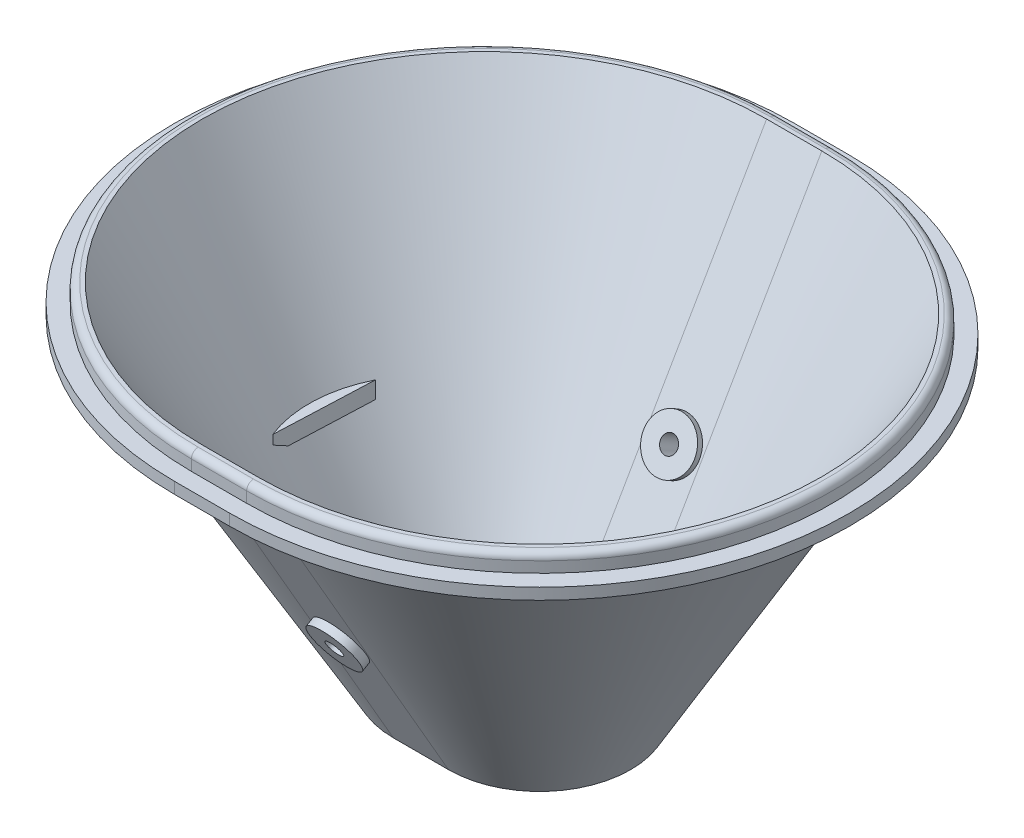
SolidWorks part; units mm, degrees
ref_plane "Front Plane" through (0, 0, 0) normal (0, 0, 1) x (1, 0, 0)
ref_plane "Top Plane" through (0, 0, 0) normal (0, 1, 0) x (1, 0, 0)
ref_plane "Right Plane" through (0, 0, 0) normal (1, 0, 0) x (0, 0, -1)
sketch3d "3DSketch3"
  line L0 (3.059, 15.8968, -14.5607) -> (7.0226, 15.8968, -14.5607)
  line L1 (7.0226, 15.8968, 14.5607) -> (-2.0226, 15.8968, 14.5607)
  line L2 (-1.9193, 15.8968, -14.5607) -> (3.059, 15.8968, -14.5607)
  arc A0 (7.0226, 15.8968, -14.5607) -> (7.0226, 15.8968, 14.5607) centre (5, 15.8968, 0) cw
  arc A3 (-2.0226, 15.8968, 14.5607) -> (-1.9193, 15.8968, -14.5607) centre (-0.0092, 15.8968, 0.007) cw
  point P3 (5, 1.1963, 0)
  point P7 (-0.0092, 1.2044, 0.007)
sketch3d "3DSketch2"
  line L0 (3.0806, 16.4804, -13.5499) -> (6.9193, 16.4804, -13.5499)
  line L1 (4.7004, 16.4804, 13.6773) -> (-0.7631, 16.4804, 13.6773)
  line L2 (-1.9193, 16.4804, -13.5499) -> (3.0806, 16.4804, -13.5499)
  arc A0 (6.9193, 16.4804, -13.5499) -> (4.7004, 16.4804, 13.6773) centre (5.0285, 16.4804, 0) cw
  arc A1 (-0.7631, 16.4804, 13.6773) -> (-1.9193, 16.4804, -13.5499) centre (0.1584, 16.4804, 0) cw
  point P5 (5.0285, 2.7991, 0)
  point P11 (0.1584, 2.772, 0)
sketch "Sketch3" plane through (0, 0, 0) normal (1, 0, 0) x (0, 0, -1)
  line L0 (13.5499, 16.4804) -> (4.7863, 0.7578)
  line L1 (4.7863, 0.7578) -> (5.7863, 0.7578)
  line L2 (5.7863, 0.7578) -> (14.6001, 16.5704)
  line L3 (18.971, 24.4121) -> (21.8382, 24.4121)
  line L4 (21.8382, 24.4121) -> (21.8382, 25.4121)
  line L5 (21.8382, 25.4121) -> (20.3382, 25.4121)
  line L6 (20.3382, 25.4121) -> (20.3382, 26.3621)
  line L7 (19.7382, 26.9621) -> (19.3923, 26.9621)
  line L8 (19.3923, 26.9621) -> (13.5499, 16.4804)
  line L9 (14.6001, 16.5704) -> (18.971, 24.4121)
  arc A0 (20.3382, 26.3621) -> (19.7382, 26.9621) centre (19.7382, 26.3621) ccw
  dimension "D7" = 0.6
  dimension "D1" = 0.3459
  dimension "D2" = 18
  dimension "D3" = 1
  dimension "D4" = 1
  dimension "D5" = 1.5
  dimension "D6" = 0.95
  dimension "D8" = 180
  dimension "D9" = 12
ref_plane "Plane for horizontal sketch" through (0, 16.4804, 0) normal (0, 1, 0) x (1, 0, 0)
sketch "Sketch4" plane through (0, 16.4804, 0) normal (0, 1, 0) x (1, 0, 0)
  line L3 (5.0285, -17.4227) -> (0.1584, -17.4227)
  line L4 (0.1584, 15.5773) -> (5.0285, 15.5773)
  arc A2 (0.1584, -17.4227) -> (0.1584, 15.5773) centre (0.1584, -0.9227) cw
  arc A3 (5.0285, 15.5773) -> (5.0285, -17.4227) centre (5.0285, -0.9227) cw
  dimension "D1" = 33
ref_plane "Plane for vertical sketch" through (0.1584, 0, 0) normal (1, 0, 0) x (0, 0, -1)
sketch "Sketch6" plane through (0.1584, 0, 0) normal (1, 0, 0) x (0, 0, -1)
  line L0 (15.5773, 16.4804) -> (6.1753, 0.1956)
  line L1 (6.1753, 0.1956) -> (7.099, 0.1956)
  line L2 (7.099, 0.1956) -> (18.6334, 20.1737)
  line L3 (23.4121, 28.4507) -> (26.4106, 28.4507)
  line L4 (26.4106, 28.4507) -> (26.4106, 29.4507)
  line L5 (26.4106, 29.4507) -> (24.9106, 29.4507)
  line L6 (24.9106, 29.4507) -> (24.9106, 30.4007)
  line L7 (24.3106, 31.0007) -> (23.9606, 31.0007)
  line L8 (23.9606, 31.0007) -> (15.5773, 16.4804)
  line L9 (18.6334, 20.1737) -> (23.4121, 28.4507)
  arc A0 (24.9106, 30.4007) -> (24.3106, 31.0007) centre (24.3106, 30.4007) ccw
  dimension "D4" = 0.6
  dimension "D2" = 1
  dimension "D3" = 1.5
  dimension "D5" = 0.35
  dimension "D6" = 0.95
  dimension "D7" = 0.8
  dimension "D8" = 60
sweep "Sweep4" add profiles "Sketch6" path "Sketch4"
sketch3d "prrrrrr"
  line L0 (2.5934, 0.1956, 8.0207) -> (2.5934, 0.1956, -6.1753) construction
  line L3 (2.5934, 0.1956, 0.9227) -> (2.5934, 8.687, 0.9227) construction
  line L4 (5.0285, 0.1956, -6.1753) -> (0.1584, 0.1956, -6.1753) construction
  line L5 (5.0285, 0.1956, 8.0207) -> (0.1584, 0.1956, 8.0207) construction
sketch "Sketch7" plane through (0, -2.6251, -4.5468) normal (0, -0.5, -0.866) x (-1, 0, 0)
  line L1 (-5.0285, 38.8277) -> (-0.1584, 38.8277) construction
  circle A0 centre (-2.5934, 17.6277) radius 2.25
  point P2 (-2.5934, 38.8277)
  dimension "D1" = 21.2
  dimension "D2" = 4.5
extrude "Boss-Extrude1" add sketch "Sketch7" along normal blind 1.5 and the other way blind 0.5
sketch "Sketch8" plane through (0, -3.4242, 5.9308) normal (0, -0.5, 0.866) x (1, 0, 0)
  line L2 (5.0285, 39.9254) -> (0.1584, 39.9254) construction
  circle A0 centre (2.5934, 18.7254) radius 2.25
  point P2 (2.5934, 39.9254)
  dimension "D1" = 21.2
extrude "Boss-Extrude2" add sketch "Sketch8" along normal blind 1.5 and the other way blind 0.5
sketch "Sketch9" plane through (0, -4.1742, 7.2299) normal (0, -0.5, 0.866) x (1, 0, 0)
  circle A0 centre (2.5934, 18.7254) radius 0.75
extrude "Cut-Extrude1" cut sketch "Sketch9" against normal up to surface (2 mm away) up to face at (2.5934, 11.0939, 13.7355)
sketch "Sketch10" plane through (0, -3.3751, -5.8458) normal (0, -0.5, -0.866) x (-1, 0, 0)
  circle A0 centre (-2.5934, 17.6277) radius 0.75
extrude "Cut-Extrude2" cut sketch "Sketch10" against normal up to surface (2 mm away) up to face at (2.5934, 14.8395, -14.0526)
ref_axis "central axis" through (2.5934, -16.8382, 0.9227) along (0, 1, 0)
ref_plane "Plane1" through (0, 13, 0) normal (0, 1, 0) x (1, 0, 0)
sketch "Sketch11" plane through (0, 13, 0) normal (0, 1, 0) x (1, 0, 0)
  arc A0 (19.2192, 3.5407) -> (18.8552, -5.1512) centre (1899.2023, -79.54) ccw
  arc A1 (19.2192, 3.5407) -> (18.8552, -5.1512) centre (9.29, -0.3971) cw
extrude "Boss-Extrude3" add sketch "Sketch11" along normal blind 1.5 separate body contours A0 A1
pattern_circular "CirPattern9" count 2 every 180 about axis through (2.5934, -16.8382, 0.9227) along (0, 1, 0) of bodies 117
sketch "Sketch12" plane through (0, -3.0251, -5.2396) normal (0, -0.5, -0.866) x (-1, 0, 0)
  text T0 "V"
extrude "Boss-Extrude4" add sketch "Sketch12" along normal blind 0.5
